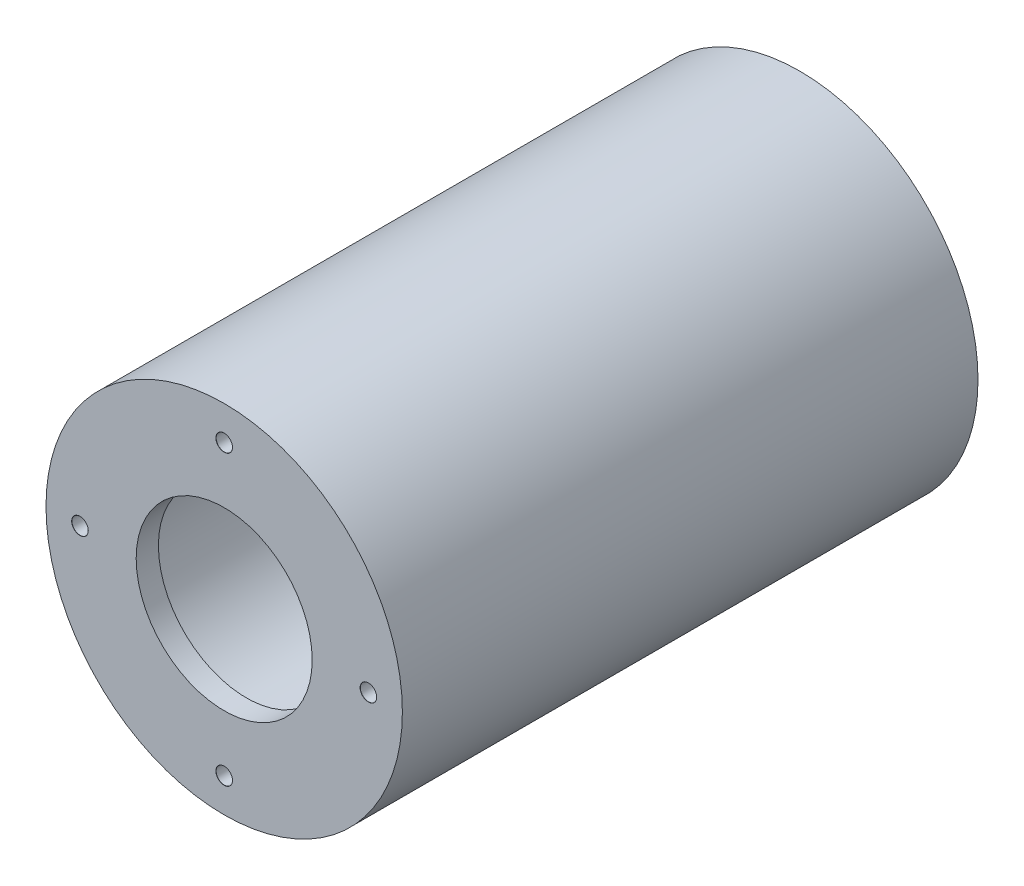
SolidWorks part; units mm, degrees
ref_plane "Front Plane" through (0, 0, 0) normal (0, 0, 1) x (1, 0, 0)
ref_plane "Top Plane" through (0, 0, 0) normal (0, 1, 0) x (1, 0, 0)
ref_plane "Right Plane" through (0, 0, 0) normal (1, 0, 0) x (0, 0, -1)
sketch "Sketch Spindle Skeleton" plane through (0, 0, 0) normal (1, 0, 0) x (0, 0, -1)
  line L5 (-1000, 0) -> (49000, 0)
  line L6 (0, -9.5) -> (0, 9.5)
  line L13 (0, 9.5) -> (-48.3, 9.5)
  line L26 (-48.3, 9.5) -> (-48.3, 14)
  line L27 (-48.3, 14) -> (-119.9, 14)
  line L32 (-119.9, 14) -> (-119.9, 9.5)
  line L33 (-119.9, 9.5) -> (-160, 9.5)
  line L34 (-160, 9.5) -> (-160, -9.5)
  line L35 (-160, -9.5) -> (-119.9, -9.5)
  line L36 (-119.9, -9.5) -> (-119.9, -14)
  line L37 (-119.9, -14) -> (-48.3, -14)
  line L38 (-48.3, -14) -> (-48.3, -9.5)
  line L39 (0, -9.5) -> (-48.3, -9.5)
  line L40 (-24.2, 36) -> (-19.2, 36)
  line L41 (-136.5, 22.5) -> (-119.9, 22.5)
  line L42 (-136.5, 22.5) -> (-136.5, -22.5)
  line L43 (-136.5, -22.5) -> (-119.9, -22.5)
  line L44 (-119.9, 22.5) -> (-119.9, -22.5)
  line L45 (-136.5, 22.5) -> (-119.9, -22.5) construction
  line L46 (-136.5, -22.5) -> (-119.9, 22.5) construction
  line L47 (-31.7, 22.5) -> (-48.3, 22.5)
  line L48 (-31.7, 22.5) -> (-31.7, -22.5)
  line L49 (-31.7, -22.5) -> (-48.3, -22.5)
  line L50 (-48.3, 22.5) -> (-48.3, -22.5)
  line L51 (-31.7, 22.5) -> (-48.3, -22.5) construction
  line L52 (-31.7, -22.5) -> (-48.3, 22.5) construction
  line L59 (-19.2, 36) -> (-19.2, -36)
  line L60 (-19.2, -36) -> (-24.2, -36)
  line L61 (-24.2, -22.5) -> (-29.2, -22.5)
  line L62 (-29.2, -22.5) -> (-29.2, -17.5)
  line L63 (-29.2, -17.5) -> (-24.2, -17.5)
  line L64 (-24.2, -17.5) -> (-24.2, 17.5)
  line L65 (-24.2, 17.5) -> (-29.2, 17.5)
  line L66 (-29.2, 17.5) -> (-29.2, 22.5)
  line L67 (-29.2, 22.5) -> (-24.2, 22.5)
  line L68 (-24.2, 22.5) -> (-24.2, 36)
  line L69 (-24.2, -22.5) -> (-24.2, -36)
  line L71 (-141.5, 36) -> (-25.2, 36)
  line L72 (-141.5, 36) -> (-141.5, -36)
  line L73 (-141.5, -36) -> (-25.2, -36)
  line L74 (-25.2, 36) -> (-25.2, -36)
  line L75 (-141.5, 36) -> (-25.2, -36) construction
  line L76 (-141.5, -36) -> (-25.2, 36) construction
  point P3 (0, 0)
  point P5 (0, 0)
  point P7 (0, 0)
  point P18 (-128.2, 0)
  point P24 (-40, 0)
  point P29 (-83.35, 0)
  point P48 (-19.2, 29.25)
sketch "Sketch1" plane through (0, 0, 0) normal (1, 0, 0) x (0, 0, -1)
  line L0 (-25.2, 36) -> (-25.2, -36) construction
  line L1 (-141.5, -36) -> (-25.2, -36) construction
  line L2 (-141.5, 36) -> (-141.5, -36) construction
  line L3 (-141.5, 36) -> (-25.2, 36) construction
  line L4 (-25.2, 36) -> (-25.2, -36)
  line L5 (-141.5, -36) -> (-25.2, -36)
  line L6 (-141.5, 36) -> (-141.5, -36)
  line L7 (-141.5, 36) -> (-25.2, 36)
  line L8 (-141.5, 17.78) -> (-137.008, 17.78)
  line L9 (-137.008, 17.78) -> (-137.008, 22.5)
  line L10 (-137.008, 22.5) -> (-25.2, 22.5)
  line L12 (-136.5, 22.5) -> (-136.5, -22.5) construction
  line L13 (-136.5, 22.5) -> (-119.9, 22.5) construction
  line L14 (-201000, 0) -> (249000, 0) construction
  line L15 (-141.5, 0) -> (-25.2, 0) construction
  dimension "D1" = 0.508
  dimension "D2" = 0
  dimension "D3" = 17.78
revolve "Revolve1" add sketch "Sketch1" angle 360 about L15 region at (0, 29.1286, 84.0949)
sketch "Sketch2" plane through (0, 0, 25.2) normal (0, 0, -1) x (-1, 0, 0)
  circle A0 centre (0, 0) radius 29.1369 construction
  point P3 (0, 29.1369)
  point P4 (29.1369, 0)
  point P5 (0, -29.1369)
  point P6 (-29.1369, 0)
  point P7 (0, 0)
  point P10 (0, 0)
hole_wizard "Tap Drill for M4x0.7 Tap1" positions "Sketch5" profile "Sketch6" hole size "M4x0.7" standard "ANSI Metric"
sketch "Sketch5" plane through (0, 0, 25.2) normal (0, 0, -1) x (-1, 0, 0)
  point P0 (0, 29.1369)
  point P3 (29.1369, 0)
  point P6 (0, -29.1369)
  point P9 (-29.1369, 0)
sketch "Sketch6" plane through (0, 29.1369, 25.2) normal (1, 0, 0) x (0, 1, 0)
  line L0 (0, 0) -> (0, 10.9914)
  line L1 (0, 10.9914) -> (1.65, 10)
  line L2 (1.65, 10) -> (1.65, 0.025)
  line L3 (1.65, 0.025) -> (1.675, 0)
  line L5 (1.675, 0) -> (0, 0)
  line L6 (-1.65, 0.025) -> (-1.675, 0) construction
  line L10 (0, 10.9914) -> (-1.65, 10) construction
  line L11 (0, -6.35) -> (0, 107.95) construction
  dimension "Hole Dia." = 3.3
  dimension "Hole Depth" = 10
  dimension "Near C'Sink Dia." = 3.35
  dimension "Near C'Sink Angle" = 90
  dimension "Drill Angle" = 118
ref_plane "Plane1" through (0, 0, 83.35) normal (0, 0, -1) x (-1, 0, 0)
mirror "Mirror1" about plane through (0, 0, 83.35) normal (0, 0, -1) of "Tap Drill for M4x0.7 Tap1"
equation "\"D2@Sketch1\"=15*10^(-6)"
